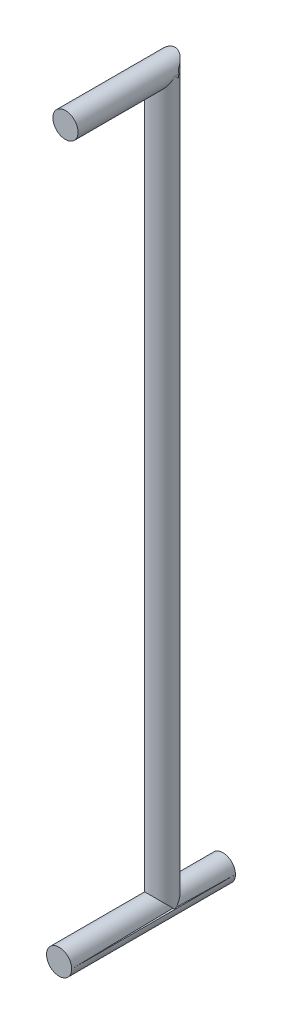
SolidWorks part; units mm, degrees
ref_plane "Front Plane" through (0, 0, 0) normal (0, 0, 1) x (1, 0, 0)
ref_plane "Top Plane" through (0, 0, 0) normal (0, 1, 0) x (1, 0, 0)
ref_plane "Right Plane" through (0, 0, 0) normal (1, 0, 0) x (0, 0, -1)
sketch "Sketch1" plane through (0, 0, 0) normal (0, 1, 0) x (1, 0, 0)
  circle A0 centre (-15.4197, 2.7019) radius 1
extrude "Boss-Extrude1" add sketch "Sketch1" along normal blind 59.28
sketch "Sketch2" plane through (0, 0, 0) normal (0, 0, 1) x (1, 0, 0)
  line L0 (-15.4197, 59.28) -> (-15.4197, 58.28)
  line L1 (-14.4197, 59.28) -> (-16.4197, 59.28) construction
  line L3 (-16.4197, 57.28) -> (-14.4197, 57.28)
  line L4 (-16.4197, 57.28) -> (-16.4197, 59.28)
  line L5 (-16.4197, 59.28) -> (-14.4197, 59.28)
  line L6 (-14.4197, 57.28) -> (-14.4197, 59.28)
  line L7 (-16.4197, 57.28) -> (-14.4197, 59.28) construction
  line L8 (-16.4197, 59.28) -> (-14.4197, 57.28) construction
  circle A0 centre (-15.4197, 58.28) radius 1
extrude "Cut-Extrude1" cut sketch "Sketch2" against normal blind 59.28 contours A0 L5 L4 | A0 L6 L5 region at (-16.1963, 59.0566, 0) region at (-14.6431, 59.0566, 0)
sketch "Sketch3" plane through (0, 0, 0) normal (0, 0, 1) x (1, 0, 0)
  line L0 (-15.4197, 59.28) -> (-15.4197, 58.28)
  arc A0 (-14.4197, 58.28) -> (-16.4197, 58.28) centre (-15.4197, 58.28) ccw construction
  circle A1 centre (-15.4197, 58.28) radius 1
extrude "Boss-Extrude2" add sketch "Sketch3" along normal blind 5 and the other way blind 3 contours A1 region at (-16.1068, 57.5929, 0)
sketch "Sketch4" plane through (0, 0, 0) normal (0, 0, 1) x (1, 0, 0)
  line L0 (-15.4197, 0) -> (-15.4197, 1)
  line L1 (-16.4197, 0) -> (-14.4197, 0) construction
  circle A0 centre (-15.4197, 1) radius 1
extrude "Boss-Extrude3" add sketch "Sketch4" against normal blind 5 from offset 2.5 contours A0 region at (-14.7326, 0.3129, 0) offset against normal yes
sketch "Sketch5" plane through (0, 0, -7.5) normal (0, 0, -1) x (-1, 0, 0)
  line L0 (15.4197, 0) -> (15.4197, 1)
  line L2 (14.4197, 2) -> (16.4197, 2)
  line L3 (14.4197, 2) -> (14.4197, 0)
  line L4 (14.4197, 0) -> (16.4197, 0)
  line L5 (16.4197, 2) -> (16.4197, 0)
  line L6 (14.4197, 2) -> (16.4197, 0) construction
  line L7 (14.4197, 0) -> (16.4197, 2) construction
  circle A0 centre (15.4197, 1) radius 1 construction
  circle A1 centre (15.4197, 1) radius 1
  circle M1 centre (15.4197, 1) radius 1
extrude "Cut-Extrude2" cut sketch "Sketch5" against normal blind 15 contours L3 L4 M1 | L5 L4 M1 region at (-14.6431, 0.2234, -7.5) region at (-16.1963, 0.2234, -7.5)
sketch "Sketch6" plane through (0, 0, -7.5) normal (0, 0, -1) x (-1, 0, 0)
  circle A0 centre (15.4197, 1) radius 1
extrude "Boss-Extrude4" add sketch "Sketch6" against normal blind 13
